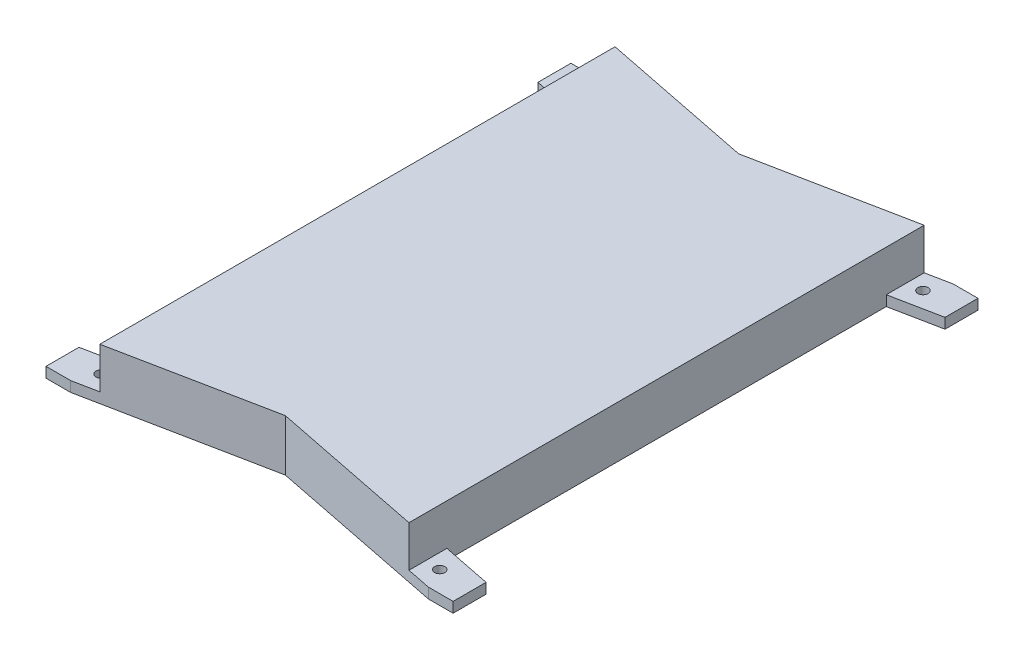
SolidWorks part; units mm, degrees
material "ABS"
ref_plane "Front Plane" through (0, 0, 0) normal (0, 0, 1) x (1, 0, 0)
ref_plane "Top Plane" through (0, 0, 0) normal (0, 1, 0) x (1, 0, 0)
ref_plane "Right Plane" through (0, 0, 0) normal (1, 0, 0) x (0, 0, -1)
ref_axis "X" through (-88.99, 0, 0) along (1, 0, 0)
ref_axis "Y" through (0, 55, 0) along (0, -1, 0)
ref_axis "Z" through (0, 0, -88.99) along (0, 0, 1)
sketch "Sketch1" plane through (0, 0, 0) normal (0, 1, 0) x (1, 0, 0)
  line L0 (-75, 106.6) -> (-75, -106.6)
  line L1 (-75, -125) -> (0, -110)
  line L2 (0, -110) -> (75, -125)
  line L3 (75, -106.6) -> (75, 106.6)
  line L4 (75, 125) -> (0, 110)
  line L5 (0, 110) -> (-75, 125)
  line L6 (0, 110) -> (0, -110) construction
  line L7 (-75, 0) -> (75, 0) construction
  line L8 (75, -125) -> (86.767, -127.3534)
  line L9 (86.767, -127.3534) -> (98.767, -127.3534)
  line L10 (98.767, -127.3534) -> (98.767, -111.3534)
  line L11 (98.767, -111.3534) -> (75, -106.6)
  line L12 (98.767, 111.3534) -> (75, 106.6)
  line L13 (98.767, 127.3534) -> (98.767, 111.3534)
  line L14 (86.767, 127.3534) -> (98.767, 127.3534)
  line L15 (75, 125) -> (86.767, 127.3534)
  line L16 (-98.767, -127.3534) -> (-98.767, -111.3534)
  line L17 (-86.767, -127.3534) -> (-98.767, -127.3534)
  line L18 (-75, -125) -> (-86.767, -127.3534)
  line L19 (-98.767, -111.3534) -> (-75, -106.6)
  line L20 (-98.767, 111.3534) -> (-75, 106.6)
  line L21 (-98.767, 127.3534) -> (-98.767, 111.3534)
  line L22 (-86.767, 127.3534) -> (-98.767, 127.3534)
  line L23 (-75, 125) -> (-86.767, 127.3534)
  line L24 (-75, 125) -> (-75, 106.6) construction
  line L25 (75, 125) -> (75, 106.6) construction
  line L26 (75, -106.6) -> (75, -125) construction
  line L27 (-75, -106.6) -> (-75, -125) construction
  dimension "D1" = 250
  dimension "D2" = 220
  dimension "D3" = 150
  dimension "D4" = 12
  dimension "D5" = 16
  dimension "D6" = 12
extrude "Boss-Extrude1" add sketch "Sketch1" along normal blind 5
sketch "Sketch3" plane through (0, 5, 0) normal (0, 1, 0) x (1, 0, 0)
  line L0 (-75, 106.6) -> (-75, 125) construction
  line L1 (0, 110) -> (-86.767, 127.3534) construction
  line L2 (75, 106.6) -> (75, 125) construction
  line L3 (86.767, 127.3534) -> (0, 110) construction
  line L4 (-75, -106.6) -> (-75, -125) construction
  line L5 (-86.767, -127.3534) -> (0, -110) construction
  line L6 (75, -106.6) -> (75, -125) construction
  line L7 (0, -110) -> (86.767, -127.3534) construction
  line L8 (-75, 106.6) -> (-75, -106.6) construction
  line L9 (75, -106.6) -> (75, 106.6) construction
  line L10 (75, 125) -> (0, 110)
  line L11 (0, 110) -> (-75, 125)
  line L12 (75, -106.6) -> (75, 106.6)
  line L13 (0, -110) -> (75, -125)
  line L14 (-75, 106.6) -> (-75, -106.6)
  line L15 (-75, -125) -> (0, -110)
  line L16 (-73, -122.5604) -> (0, -107.9604)
  line L17 (0, -107.9604) -> (73, -122.5604)
  line L18 (73, -106.6) -> (73, -122.5604)
  line L19 (73, -106.6) -> (73, 106.6)
  line L20 (73, 106.6) -> (73, 122.5604)
  line L21 (73, 122.5604) -> (0, 107.9604)
  line L22 (0, 107.9604) -> (-73, 122.5604)
  line L23 (-73, 106.6) -> (-73, 122.5604)
  line L24 (-73, 106.6) -> (-73, -106.6)
  line L25 (-73, -106.6) -> (-73, -122.5604)
  line L26 (75, 0) -> (-75, 0) construction
  line L27 (0, -110) -> (0, 110) construction
  line L28 (80.4076, -126.0815) -> (83.9461, -108.3892) construction
  line L29 (98.767, -111.3534) -> (75, -106.6) construction
  circle A0 centre (82.1768, -117.2354) radius 2.5
  circle A1 centre (-82.1768, -117.2354) radius 2.5
  circle A2 centre (-82.1768, 117.2354) radius 2.5
  circle A3 centre (82.1768, 117.2354) radius 2.5
  dimension "D2" = 5
  dimension "D3" = 82
  dimension "D1" = 2
extrude "Cut-Extrude1" cut sketch "Sketch3" against normal through all contours L24 L25 L16 L17 L18 L19 L20 L21 L22 L23 | A1 | A0 | A2 | A3 region at (0, 5, 0) region at (82.1768, 5, 117.2354) region at (-82.1768, 5, 117.2354) region at (-82.1768, 5, -117.2354) region at (82.1768, 5, -117.2354)
sketch "Sketch4" plane through (0, 5, 0) normal (0, 1, 0) x (1, 0, 0)
  line L0 (0, -107.9604) -> (73, -122.5604) construction
  line L1 (-73, -122.5604) -> (0, -107.9604) construction
  line L2 (73, 122.5604) -> (73, -122.5604) construction
  line L3 (73, 122.5604) -> (0, 107.9604) construction
  line L4 (0, 107.9604) -> (-73, 122.5604) construction
  line L5 (-73, 122.5604) -> (-73, -122.5604) construction
  line L6 (0, -107.9604) -> (73, -122.5604)
  line L7 (-73, -122.5604) -> (0, -107.9604)
  line L8 (73, 122.5604) -> (73, -122.5604)
  line L9 (73, 122.5604) -> (0, 107.9604)
  line L10 (0, 107.9604) -> (-73, 122.5604)
  line L11 (-73, 122.5604) -> (-73, -122.5604)
  line L12 (-75, 125) -> (-75, -125)
  line L13 (-75, -125) -> (0, -110)
  line L14 (0, -110) -> (75, -125)
  line L15 (75, 125) -> (75, -125)
  line L16 (75, 125) -> (0, 110)
  line L17 (0, 110) -> (-75, 125)
  dimension "D1" = 2
extrude "Boss-Extrude2" add sketch "Sketch4" along normal blind 20
sketch "Sketch5" plane through (0, 25, 0) normal (0, 1, 0) x (1, 0, 0)
  line L0 (75, 125) -> (0, 110) construction
  line L1 (0, 110) -> (-75, 125) construction
  line L2 (-75, 125) -> (-75, -125) construction
  line L3 (-75, -125) -> (0, -110) construction
  line L4 (0, -110) -> (75, -125) construction
  line L5 (75, -125) -> (75, 125) construction
  line L6 (75, 125) -> (0, 110)
  line L7 (0, 110) -> (-75, 125)
  line L8 (-75, 125) -> (-75, -125)
  line L9 (-75, -125) -> (0, -110)
  line L10 (0, -110) -> (75, -125)
  line L11 (75, -125) -> (75, 125)
extrude "Boss-Extrude3" add sketch "Sketch5" against normal blind 5
sketch "Sketch6" plane through (21.1538, 0, -105.7692) normal (0.1961, 0, -0.9806) x (-0.9806, 0, -0.1961)
  line L0 (31.5728, 2) -> (38.3228, 2)
  line L1 (31.5728, 4.75) -> (38.3228, 4.75)
  line L2 (21.5728, 0) -> (110.0581, 0) construction
  line L3 (21.5728, 25) -> (21.5728, 0) construction
  arc A1 (38.3228, 2) -> (38.3228, 4.75) centre (38.3228, 3.375) ccw
  arc A2 (31.5728, 2) -> (31.5728, 4.75) centre (31.5728, 3.375) cw
  point P6 (50.9202, 8.1458)
  dimension "D1" = 6.75
  dimension "D2" = 2.75
  dimension "D3" = 2
  dimension "D4" = 10
extrude "Cut-Extrude2" cut sketch "Sketch6" against normal up to surface (2 mm away) up to face at (-36.5, 10, -115.2604)
